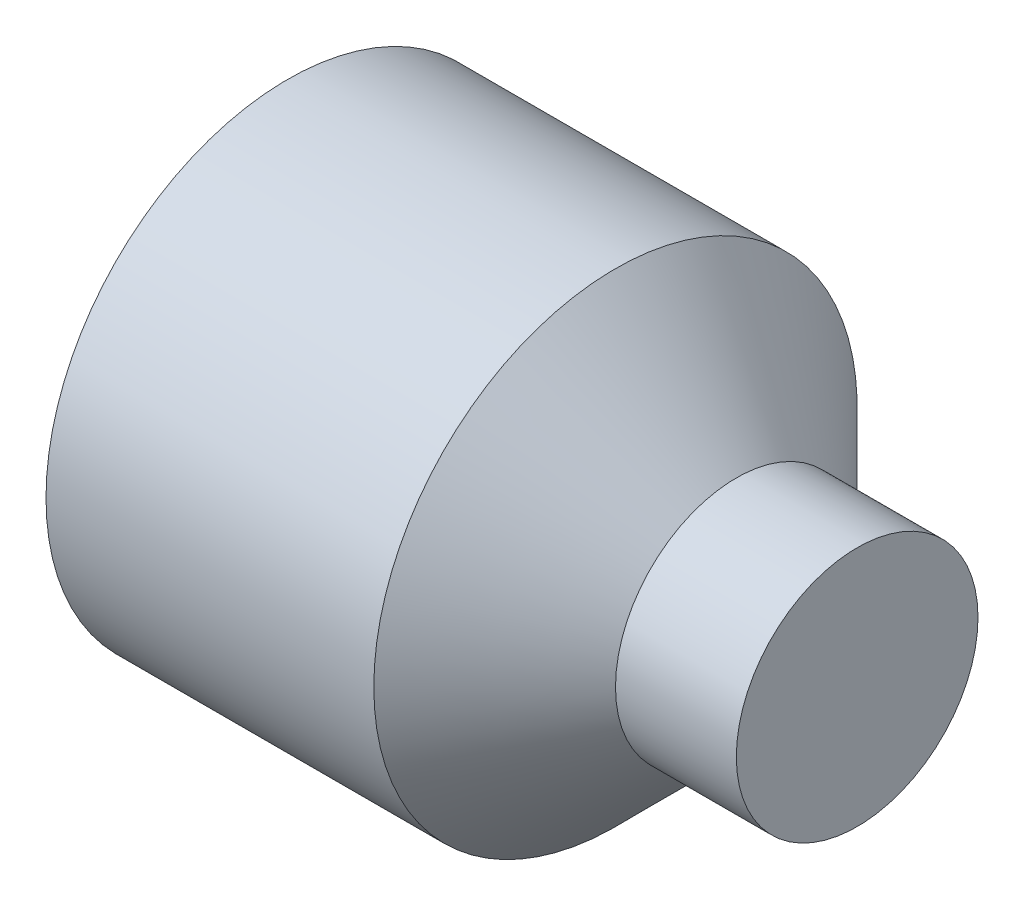
SolidWorks part; units mm, degrees
ref_plane "Front Plane" through (0, 0, 0) normal (0, 0, 1) x (1, 0, 0)
ref_plane "Top Plane" through (0, 0, 0) normal (0, 1, 0) x (1, 0, 0)
ref_plane "Right Plane" through (0, 0, 0) normal (1, 0, 0) x (0, 0, -1)
sketch "BodySke" plane through (0, 0, 0) normal (0, 0, 1) x (1, 0, 0)
  line L0 (0, 0) -> (3.28, 0) construction
  line L1 (2, 0) -> (2, 0.4)
  line L2 (1.2, 0.8) -> (1.6, 0.4)
  line L3 (1.2, 0.8) -> (0, 0.8)
  line L4 (0, 0.8) -> (0, 0)
  line L5 (0, 0) -> (2, 0)
  line L6 (1.65, 1.0236) -> (1.65, -0.6432) construction
  line L7 (1.6, 0.4) -> (2, 0.4)
  point P5 (0, 0.601)
  dimension "Minor_dia" = 1.202
  dimension "D1" = 135
  dimension "Advance" = 0.35
revolve "BaseBody" add sketch "BodySke" angle 360 about L0
cosmetic thread "ThreadCosmetic" [suppressed] parameters "Minor_dia"=1.202
sketch "HeadChamferSke" plane through (0, 0, 0) normal (0, 0, 1) x (1, 0, 0)
  line L0 (0, 0) -> (2.4505, 0) construction
  line L1 (0, 0.8) -> (0, 0.601)
  line L2 (0, 0.8) -> (0.1149, 0.8)
  line L3 (0.1149, 0.8) -> (0, 0.601)
  line L5 (0, 0.8) -> (0, -0.8) construction
  line L6 (0, 0.8) -> (0, 0) construction
  line L7 (1.2, 0.8) -> (0, 0.8) construction
  dimension "Angle" = 30
revolve "HeadChamfer" cut sketch "HeadChamferSke" angle 360 about L0
sketch "HexagonSocketSke" plane through (0, 0, 0) normal (-1, 0, 0) x (0, 0, 1)
  line L1 (0, 0.4041) -> (-0.35, 0.2021)
  line L2 (-0.35, 0.2021) -> (-0.35, -0.2021)
  line L3 (-0.35, -0.2021) -> (0, -0.4041)
  line L4 (0, -0.4041) -> (0.35, -0.2021)
  line L5 (0.35, -0.2021) -> (0.35, 0.2021)
  line L6 (0.35, 0.2021) -> (0, 0.4041)
  circle A0 centre (0, 0) radius 0.35 construction
  dimension "Hexagon_Width" = 0.7
extrude "HexagonSocket" cut sketch "HexagonSocketSke" against normal blind 0.7
sketch "ThdSchSke" plane through (0, 0, 0) normal (0, 0, 1) x (1, 0, 0)
  line L0 (0, 0) -> (2.6881, 0) construction
  line L1 (0.2351, 1.0298) -> (0.2351, 0.8)
  line L2 (0.2351, 1.0298) -> (0.4649, 1.0298)
  line L3 (0.4649, 1.0298) -> (0.4649, 0.8)
  line L4 (0.4649, 0.8) -> (0.35, 0.601)
  line L5 (0.35, 0.601) -> (0.2351, 0.8)
  line L8 (1.2, 0.8) -> (0.1149, 0.8) construction
  dimension "D1" = 0.35
revolve "ThreadSchematic" [suppressed] cut sketch "ThdSchSke" angle 360 about L0
pattern_linear "ThdSchPat" [suppressed] count 3 along (1, 0, 0) of bodies 104
equation "\"Minor_dia@ThreadCosmetic\" = \"Minor_dia@BodySke\""
equation "\"D1@ThdSchSke\" = \"Advance@BodySke\""
equation "\"Advance@ThdSchPat\" = \"Advance@BodySke\""
equation "\"D1@ThdSchPat\" =  int( ( \"Length@BodySke\" - \"Length_Dog@BodySke\" -  ( \"Diameter@BodySke\" / 2 - \"Chamfer_End@BodySke\" / 2 )  )  / \"Advance@BodySke\") "
